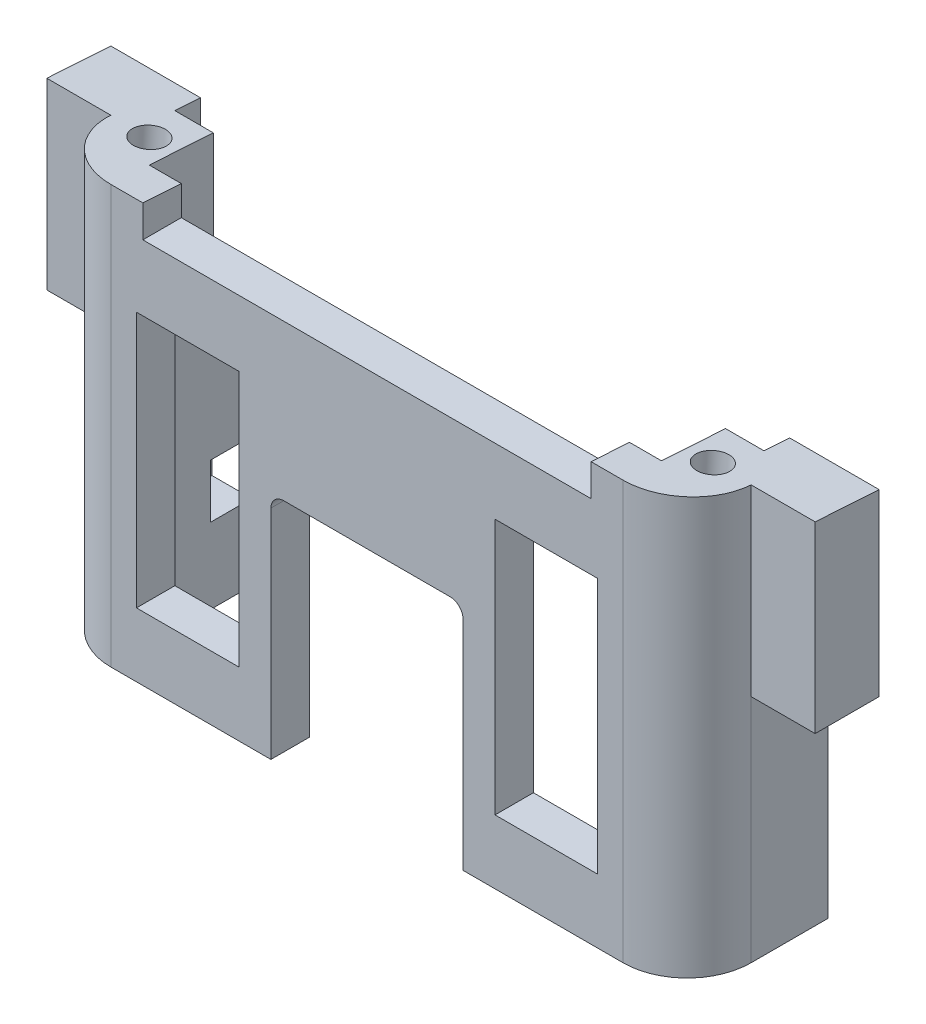
SolidWorks part; units mm, degrees
ref_plane "Front Plane" through (0, 0, 0) normal (0, 0, 1) x (1, 0, 0)
ref_plane "Top Plane" through (0, 0, 0) normal (0, 1, 0) x (1, 0, 0)
ref_plane "Right Plane" through (0, 0, 0) normal (1, 0, 0) x (0, 0, -1)
sketch "Sketch2" plane through (0, 0, 0) normal (0, 1, 0) x (1, 0, 0)
  line L0 (-25, 0) -> (25, 0)
  line L1 (25, 0) -> (25, 11)
  line L2 (-25, 0) -> (-25, 11)
  line L3 (25, 11) -> (20, 11)
  line L4 (20, 11) -> (20, 3)
  line L5 (20, 3) -> (-20, 3)
  line L6 (-20, 3) -> (-20, 11)
  line L7 (-20, 11) -> (-25, 11)
  point P4 (0, 0)
  dimension "D1" = 5
  dimension "D2" = 11
  dimension "D3" = 40
  dimension "D4" = 3
extrude "Boss-Extrude1" add sketch "Sketch2" along normal mid plane 32.64
sketch "Sketch3" plane through (0, 0, 0) normal (0, 0, 1) x (1, 0, 0)
  line L0 (25, 16.32) -> (25, -16.32) construction
  line L1 (10, -11.32) -> (18, -11.32)
  line L2 (10, -11.32) -> (10, 8.68)
  line L3 (10, 8.68) -> (18, 8.68)
  line L4 (18, -11.32) -> (18, 8.68)
  line L5 (10, -11.32) -> (18, 8.68) construction
  line L6 (10, 8.68) -> (18, -11.32) construction
  line L7 (-25, -16.32) -> (25, -16.32) construction
  line L8 (0, 0) -> (0, 16.32) construction
  line L9 (-25, 16.32) -> (25, 16.32) construction
  line L10 (-10, 8.68) -> (-18, 8.68)
  line L11 (-18, -11.32) -> (-18, 8.68)
  line L12 (-10, -11.32) -> (-18, -11.32)
  line L13 (-10, -11.32) -> (-10, 8.68)
  line L15 (-7.5, 1.68) -> (7.5, 1.68)
  line L16 (-7.5, 1.68) -> (-7.5, -16.32)
  line L17 (-7.5, -16.32) -> (7.5, -16.32)
  line L18 (7.5, 1.68) -> (7.5, -16.32)
  line L19 (-7.5, 1.68) -> (7.5, -16.32) construction
  line L20 (-7.5, -16.32) -> (7.5, 1.68) construction
  point P0 (14, -1.32)
  point P18 (0, -7.32)
  dimension "D1" = 7
  dimension "D2" = 20
  dimension "D3" = 8
  dimension "D4" = 5
  dimension "D5" = 18
  dimension "D6" = 15
extrude "Cut-Extrude1" cut sketch "Sketch3" against normal blind 4
sketch "Sketch4" plane through (0, 0, 0) normal (1, 0, 0) x (0, 0, -1)
  line L0 (0, -16.32) -> (11, -16.32) construction
  line L1 (11, 16.32) -> (10, 16.32)
  line L2 (11, 16.32) -> (11, -3.32)
  line L3 (11, -3.32) -> (10, -3.32)
  line L4 (10, 16.32) -> (10, -3.32)
  dimension "D1" = 13
  dimension "D2" = 1
extrude "Cut-Extrude2" cut sketch "Sketch4" against normal mid plane 55
fillet "Fillet1" radius 5 2 edges at (-25, 0, 0) (25, 0, 0)
sketch "Sketch5" plane through (0, 0, 0) normal (1, 0, 0) x (0, 0, -1)
  line L0 (10, 16.32) -> (0, 16.32)
  line L1 (0, 16.32) -> (10, 15.68)
  line L2 (10, 16.32) -> (10, -3.32) construction
  line L3 (10, 15.68) -> (10, 16.32)
  dimension "D1" = 0.64
extrude "Cut-Extrude3" cut sketch "Sketch5" against normal mid plane 52
sketch "Sketch6" plane through (0, 0, 0) normal (1, 0, 0) x (0, 0, -1)
  line L0 (10, 15.68) -> (5, 16)
  line L1 (5, 16) -> (5, 1.68)
  line L2 (5, -16.32) -> (5, 16) construction
  line L3 (5, 1.68) -> (10, 1.68)
  line L4 (10, 15.68) -> (10, -3.32) construction
  line L5 (10, 1.68) -> (10, 15.68)
  dimension "D1" = 14
extrude "Boss-Extrude2" add sketch "Sketch6" against normal blind 5 from surface starting at face at (-25, -1.2667, -8.6667)
extrude "Boss-Extrude3" add sketch "Sketch6<2>" along normal blind 5 from surface starting at face at (25, -1.2667, -8.6667)
sketch "Sketch6<2>" plane through (0, 0, 0) normal (1, 0, 0) x (0, 0, -1) same geometry as "Sketch6"
ref_plane "Plane1" through (0, 16.2534, -1.0402) normal (0, 0.998, -0.0639) x (1, 0, 0)
sketch "Sketch7" plane through (0, 16.2534, -1.0402) normal (0, 0.998, -0.0639) x (1, 0, 0)
  line L0 (30, 8.9781) -> (30, 3.9679) construction
  line L1 (-30, 8.9781) -> (-30, 3.9679) construction
  line L2 (-30, 8.9781) -> (-20, 8.9781) construction
  circle A0 centre (22, 3.9781) radius 1.25
  circle A1 centre (-22, 3.9781) radius 1.25
  dimension "D1" = 8
  dimension "D2" = 8
  dimension "D3" = 5
  dimension "D4" = 2.5
extrude "Cut-Extrude4" cut sketch "Sketch7" against normal blind 5
sketch "Sketch8" plane through (0, 0, 0) normal (0, 0, 1) x (1, 0, 0)
  line L0 (-20, 16.32) -> (20, 16.32) construction
  line L1 (-17.5, 18.82) -> (17.5, 18.82)
  line L2 (-17.5, 18.82) -> (-17.5, 13.82)
  line L3 (-17.5, 13.82) -> (17.5, 13.82)
  line L4 (17.5, 18.82) -> (17.5, 13.82)
  line L5 (-17.5, 18.82) -> (17.5, 13.82) construction
  line L6 (-17.5, 13.82) -> (17.5, 18.82) construction
  point P0 (0, 16.32)
  dimension "D1" = 35
  dimension "D2" = 5
extrude "Cut-Extrude5" cut sketch "Sketch8" against normal blind 5 from surface starting at face at (14, -1.32, 0)
sketch "Sketch9" plane through (0, 0, 0) normal (0, 0, 1) x (1, 0, 0)
  line L1 (-28.1, 9.78) -> (-25.9, 9.78)
  line L2 (-28.1, 9.78) -> (-28.1, 4.58)
  line L3 (-28.1, 4.58) -> (-25.9, 4.58)
  line L4 (-25.9, 9.78) -> (-25.9, 4.58)
  line L5 (-28.1, 9.78) -> (-25.9, 4.58) construction
  line L6 (-28.1, 4.58) -> (-25.9, 9.78) construction
  line L8 (-30, 16) -> (-30, 1.68) construction
  line L9 (0, 0) -> (0, 13.82) construction
  line L10 (-17.5, 13.82) -> (17.5, 13.82) construction
  line L11 (28.1, 4.58) -> (25.9, 4.58)
  line L12 (25.9, 9.78) -> (25.9, 4.58)
  line L13 (28.1, 9.78) -> (25.9, 9.78)
  line L14 (28.1, 9.78) -> (28.1, 4.58)
  line L15 (-30, 1.68) -> (-25, 1.68) construction
  point P0 (-27, 7.18)
  point P9 (-30, 8.84)
  dimension "D1" = 2.2
  dimension "D2" = 5.2
  dimension "D3" = 2.9
  dimension "D4" = 1.9
extrude "Cut-Extrude6" cut sketch "Sketch9" along normal blind 3.2 from surface starting at face at (25, 4.68, -10)
sketch "Sketch10" plane through (0, 0, 0) normal (0, 1, 0) x (1, 0, 0)
  line L0 (-20, 11) -> (-25, 11) construction
  line L1 (-25, 11) -> (-25, 5) construction
  line L2 (25, 5) -> (25, 11) construction
  circle A0 centre (-22.5, 5) radius 1.25
  circle A1 centre (22.5, 5) radius 1.25
  dimension "D1" = 6
  dimension "D2" = 2.5
  dimension "D3" = 2.5
  dimension "D4" = 2.5
extrude "Cut-Extrude7" cut sketch "Sketch10" along normal blind 5 from surface starting at face at (-18.0051, -16.32, -4.5664)
sketch "Sketch11" plane through (0, 0, 0) normal (0, 0, 1) x (1, 0, 0)
  line L0 (25, -16.32) -> (20, -16.32) construction
  line L1 (23.1, -6.22) -> (19.9, -6.22)
  line L2 (23.1, -6.22) -> (23.1, -10.42)
  line L3 (23.1, -10.42) -> (19.9, -10.42)
  line L4 (19.9, -6.22) -> (19.9, -10.42)
  line L5 (23.1, -6.22) -> (19.9, -10.42) construction
  line L6 (23.1, -10.42) -> (19.9, -6.22) construction
  line L7 (25, -3.32) -> (25, -16.32) construction
  line L8 (0, 0) -> (0, 13.82) construction
  line L9 (-17.5, 13.82) -> (17.5, 13.82) construction
  line L10 (-23.1, -10.42) -> (-19.9, -10.42)
  line L11 (-23.1, -6.22) -> (-23.1, -10.42)
  line L12 (-23.1, -6.22) -> (-19.9, -6.22)
  line L13 (-19.9, -6.22) -> (-19.9, -10.42)
  point P0 (21.5, -8.32)
  dimension "D1" = 5.9
  dimension "D2" = 4.2
  dimension "D3" = 3.2
  dimension "D4" = 1.9
extrude "Cut-Extrude8" cut sketch "Sketch11" along normal blind 3.2 from surface starting at face at (22.5, -9.82, -11)
sketch "Sketch12" plane through (0, 0, 0) normal (0, 1, 0) x (1, 0, 0)
  line L1 (20, 10) -> (23, 10)
  line L2 (20, 10) -> (20, 8)
  line L3 (20, 8) -> (23, 8)
  line L4 (23, 10) -> (23, 8)
  line L5 (-20, 10) -> (-23, 10)
  line L6 (-20, 10) -> (-20, 8)
  line L7 (-20, 8) -> (-23, 8)
  line L8 (-23, 10) -> (-23, 8)
  dimension "D1" = 3
  dimension "D2" = 2
extrude "Cut-Extrude9" cut sketch "Sketch12" along normal blind 15 from offset 2
fillet "Fillet3" radius 1 2 edges at (-7.5, 1.68, -1.5) (7.5, 1.68, -1.5)
